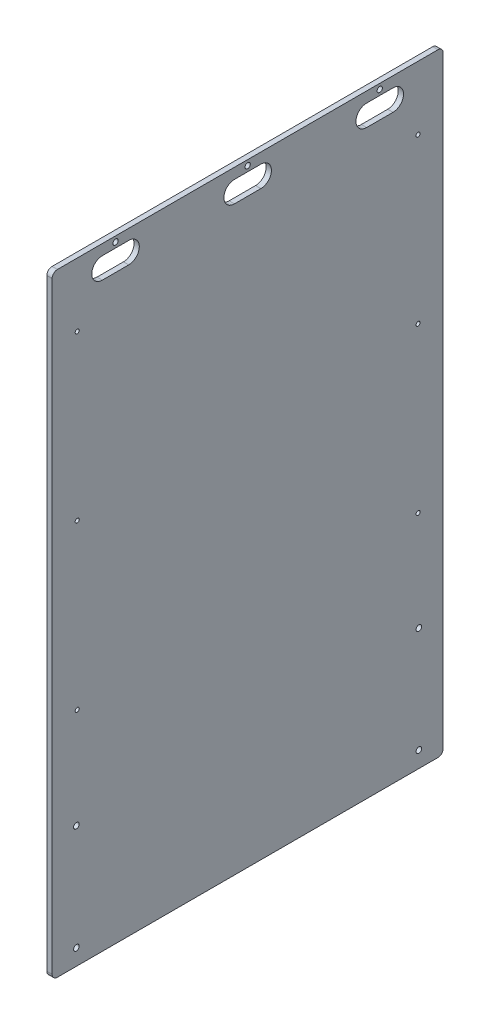
SolidWorks part; units mm, degrees
material "PC High Viscosity"
ref_plane "Front Plane" through (0, 0, 0) normal (0, 0, 1) x (1, 0, 0)
ref_plane "Top Plane" through (0, 0, 0) normal (0, 1, 0) x (1, 0, 0)
ref_plane "Right Plane" through (0, 0, 0) normal (1, 0, 0) x (0, 0, -1)
sketch "Sketch1" plane through (0, 0, 0) normal (1, 0, 0) x (0, 0, -1)
  line L1 (-234.95, -368.3) -> (234.95, -368.3)
  line L2 (-234.95, -368.3) -> (-234.95, 368.3)
  line L3 (-234.95, 368.3) -> (234.95, 368.3)
  line L4 (234.95, -368.3) -> (234.95, 368.3)
  line L5 (-234.95, -368.3) -> (234.95, 368.3) construction
  line L6 (-234.95, 368.3) -> (234.95, -368.3) construction
  point P0 (0, 0)
  dimension "D1" = 736.6
  dimension "D2" = 469.9
extrude "Boss-Extrude1" add sketch "Sketch1" along normal blind 6.35
hole_wizard "#10 (0.1935) Diameter Hole1" positions "Sketch2" profile "Sketch3" hole size "#10" standard "ANSI Inch" end condition through all
sketch "Sketch2" plane through (6.35, 0, 0) normal (1, 0, 0) x (0, 0, -1)
  line L0 (-204.7875, 291.846) -> (-204.7875, 94.996) construction
  line L1 (-204.7875, 94.996) -> (-204.7875, -101.854) construction
  line L3 (234.95, 368.3) -> (-234.95, 368.3) construction
  line L4 (-234.95, 368.3) -> (-234.95, -368.3) construction
  line L5 (204.7875, 291.846) -> (204.7875, -101.854) construction
  line L7 (-204.7875, 291.846) -> (-234.95, 291.846) construction
  line L9 (204.7875, 291.846) -> (234.95, 291.846) construction
  line L10 (234.95, -368.3) -> (234.95, 368.3) construction
  point P0 (-204.7875, 291.846)
  point P2 (-204.7875, 94.996)
  point P4 (-204.7875, -101.854)
  point P21 (204.7875, 94.996)
  point P26 (204.7875, 291.846)
  point P29 (204.7875, -101.854)
  dimension "D1" = 76.454
  dimension "D2" = 30.1625
  dimension "D3" = 196.85
sketch "Sketch3" plane through (6.35, 291.846, 204.7875) normal (0, 1, 0) x (0, 0, -1)
  line L0 (0, 0) -> (0, 6.35)
  line L1 (0, 6.35) -> (2.4574, 6.35)
  line L2 (2.4574, 6.35) -> (2.4574, 0)
  line L5 (2.4574, 0) -> (0, 0)
  line L11 (0, -6.35) -> (0, 107.95) construction
  dimension "Thru Hole Dia." = 4.9149
  dimension "Thru Hole Depth" = 6.35
hole_wizard "H (0.266) Diameter Hole1" positions "Sketch4" profile "Sketch5" hole size "H" standard "ANSI Inch" end condition through all
sketch "Sketch4" plane through (6.35, 0, 0) normal (1, 0, 0) x (0, 0, -1)
  line L0 (-234.95, -368.3) -> (234.95, -368.3) construction
  line L4 (-234.95, 368.3) -> (-234.95, -368.3) construction
  line L5 (-205.74, -348.996) -> (-234.95, -348.996) construction
  line L7 (205.74, -348.996) -> (234.95, -348.996) construction
  line L8 (234.95, -368.3) -> (234.95, 368.3) construction
  point P0 (-205.74, -221.996)
  point P2 (-205.74, -348.996)
  point P20 (205.74, -221.996)
  point P22 (205.74, -348.996)
  dimension "D1" = 19.304
  dimension "D2" = 29.21
  dimension "D3" = 127
sketch "Sketch5" plane through (6.35, -221.996, 205.74) normal (0, 1, 0) x (0, 0, -1)
  line L0 (0, 0) -> (0, 6.35)
  line L1 (0, 6.35) -> (3.3782, 6.35)
  line L2 (3.3782, 6.35) -> (3.3782, 0)
  line L5 (3.3782, 0) -> (0, 0)
  line L11 (0, -6.35) -> (0, 107.95) construction
  dimension "Thru Hole Dia." = 6.7564
  dimension "Thru Hole Depth" = 6.35
sketch "Sketch7" plane through (6.35, 0, 0) normal (1, 0, 0) x (0, 0, -1)
  line L0 (-234.95, 361.95) -> (-158.75, 361.95) construction
  line L1 (-234.95, 368.3) -> (-234.95, -368.3) construction
  line L2 (-158.75, 342.9) -> (0, 342.9) construction
  line L3 (0, 342.9) -> (158.75, 342.9) construction
  line L6 (234.95, 368.3) -> (-234.95, 368.3) construction
  line L7 (-174.625, 342.9) -> (-142.875, 342.9) construction
  line L8 (-174.625, 355.6) -> (-142.875, 355.6)
  line L9 (-174.625, 330.2) -> (-142.875, 330.2)
  line L10 (-15.875, 342.9) -> (15.875, 342.9) construction
  line L11 (-15.875, 355.6) -> (15.875, 355.6)
  line L12 (-15.875, 330.2) -> (15.875, 330.2)
  line L13 (142.875, 342.9) -> (174.625, 342.9) construction
  line L14 (142.875, 355.6) -> (174.625, 355.6)
  line L15 (142.875, 330.2) -> (174.625, 330.2)
  arc A3 (-174.625, 355.6) -> (-174.625, 330.2) centre (-174.625, 342.9) ccw
  arc A4 (-142.875, 330.2) -> (-142.875, 355.6) centre (-142.875, 342.9) ccw
  arc A5 (-15.875, 355.6) -> (-15.875, 330.2) centre (-15.875, 342.9) ccw
  arc A6 (15.875, 330.2) -> (15.875, 355.6) centre (15.875, 342.9) ccw
  arc A7 (142.875, 355.6) -> (142.875, 330.2) centre (142.875, 342.9) ccw
  arc A8 (174.625, 330.2) -> (174.625, 355.6) centre (174.625, 342.9) ccw
  point P16 (-158.75, 342.9)
  point P22 (0, 342.9)
  point P29 (158.75, 342.9)
  dimension "D6" = 12.7
  dimension "D1" = 6.35
  dimension "D2" = 76.2
  dimension "D4" = 31.75
  dimension "D5" = 19.05
extrude "Cut-Extrude1" cut sketch "Sketch7" against normal through all
fillet "Fillet1" radius 6.35 4 edges at (3.175, -368.3, -234.95) (3.175, -368.3, 234.95) (3.175, 368.3, 234.95) (3.175, 368.3, -234.95)
hole_wizard "E (0.25) Diameter Hole1" positions "Sketch8" profile "Sketch9" hole size "E" standard "ANSI Inch" end condition through all
sketch "Sketch8" plane through (6.35, 0, 0) normal (1, 0, 0) x (0, 0, -1)
  line L0 (228.6, 368.3) -> (-228.6, 368.3) construction
  line L1 (-158.75, 361.95) -> (0, 361.95) construction
  line L2 (0, 361.95) -> (158.75, 361.95) construction
  point P0 (-158.75, 361.95)
  point P2 (0, 361.95)
  point P4 (158.75, 361.95)
  dimension "D1" = 6.35
  dimension "D2" = 158.75
sketch "Sketch9" plane through (6.35, 361.95, 158.75) normal (0, 1, 0) x (0, 0, -1)
  line L0 (0, 0) -> (0, 6.35)
  line L1 (0, 6.35) -> (3.175, 6.35)
  line L2 (3.175, 6.35) -> (3.175, 0)
  line L5 (3.175, 0) -> (0, 0)
  line L11 (0, -6.35) -> (0, 107.95) construction
  dimension "Thru Hole Dia." = 6.35
  dimension "Thru Hole Depth" = 6.35
